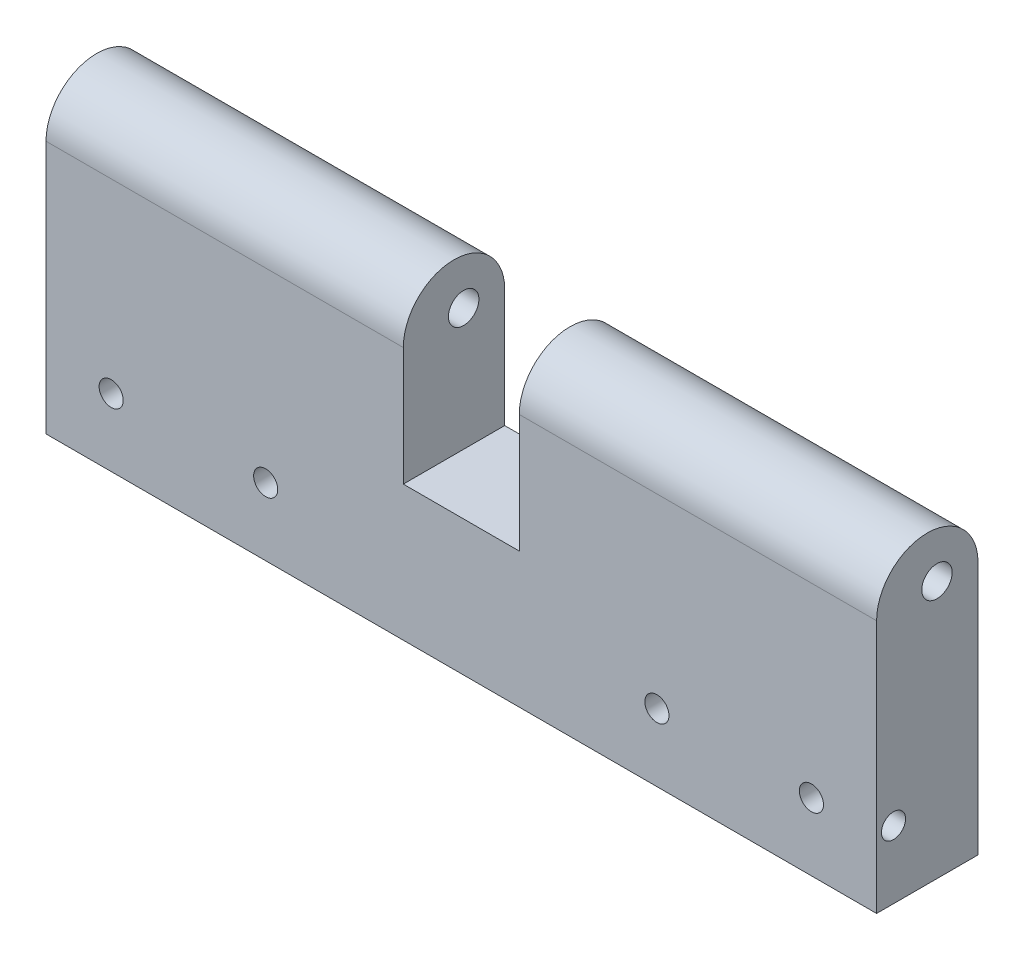
SolidWorks part; units mm, degrees
ref_plane "前视基准面" through (0, 0, 0) normal (0, 0, 1) x (1, 0, 0)
ref_plane "上视基准面" through (0, 0, 0) normal (0, 1, 0) x (1, 0, 0)
ref_plane "右视基准面" through (0, 0, 0) normal (1, 0, 0) x (0, 0, -1)
sketch "草图1" plane through (0, 0, 0) normal (0, 0, 1) x (1, 0, 0)
  line L0 (0, 14) -> (0, -14) construction
  line L1 (86.01, -14) -> (-86.01, -14)
  line L2 (86.01, -14) -> (86.01, 14)
  line L3 (86.01, 14) -> (-86.01, 14)
  line L4 (-86.01, -14) -> (-86.01, 14)
  line L5 (86.01, -14) -> (-86.01, 14) construction
  line L6 (86.01, 14) -> (-86.01, -14) construction
  circle A0 centre (-72.51, 0) radius 2.5
  circle A1 centre (-40.51, 0) radius 2.5
  circle A2 centre (40.51, 0) radius 2.5
  circle A3 centre (72.51, 0) radius 2.5
  point P0 (0, 0)
  dimension "D3" = 13.5
  dimension "D4" = 14
  dimension "D5" = 5
  dimension "D6" = 5
  dimension "D7" = 32
  dimension "D1" = 172.02
  dimension "D2" = 28
extrude "凸台-拉伸1" add sketch "草图1" along normal blind 21
sketch "草图2" plane through (0, 14, 0) normal (0, 1, 0) x (1, 0, 0)
  line L0 (86.01, 0) -> (-86.01, 0) construction
  line L1 (-86.01, 0) -> (-12.01, 0)
  line L2 (-86.01, 0) -> (-86.01, -21)
  line L3 (-86.01, -21) -> (-12.01, -21)
  line L4 (-12.01, 0) -> (-12.01, -21)
  line L5 (86.01, -21) -> (-86.01, -21) construction
  line L6 (86.01, -21) -> (86.01, 0) construction
  line L7 (86.01, 0) -> (12.01, 0)
  line L8 (86.01, 0) -> (86.01, -21)
  line L9 (86.01, -21) -> (12.01, -21)
  line L10 (12.01, 0) -> (12.01, -21)
  dimension "D1" = 74
  dimension "D2" = 74
extrude "凸台-拉伸2" add sketch "草图2" along normal blind 35
sketch "草图3" plane through (86.01, 0, 0) normal (1, 0, 0) x (0, 0, -1)
  line L0 (-21, 49) -> (0, 49) construction
  line L1 (-21, -14) -> (-21, 49) construction
  line L2 (-21, 49) -> (0, 49)
  line L3 (-21, 49) -> (-21, 38.5)
  line L4 (-21, 38.5) -> (0, 38.5)
  line L5 (0, 49) -> (0, 38.5)
  circle A0 centre (-10.5, 38.5) radius 10.5
  line M5 (0, -14) -> (0, 49)
  line M6 (0, 49) -> (-21, 49)
  line M7 (-21, 49) -> (-21, -14)
  dimension "D1" = 10.5
  dimension "D2" = 21
  dimension "D3" = 10.5
extrude "切除-拉伸1" cut sketch "草图3" against normal through all contours A0 M5 M6 | A0 L2 M7 region at (86.01, 46.6546, 18.6546) region at (86.01, 46.6546, 2.3454)
sketch "草图4" plane through (86.01, 0, 0) normal (1, 0, 0) x (0, 0, -1)
  circle A0 centre (-8.5002, 39.35) radius 3.15
  dimension "D1" = 6.3
extrude "切除-拉伸2" cut sketch "草图4" against normal through all
sketch "草图6" plane through (86.01, 0, 0) normal (1, 0, 0) x (0, 0, -1)
  circle A0 centre (-17.5, 0) radius 2.5
extrude "切除-拉伸3" cut sketch "草图6" against normal blind 8
sketch "草图7" plane through (-86.01, 0, 0) normal (-1, 0, 0) x (0, 0, 1)
  circle A0 centre (17.5, 0) radius 2.5
extrude "切除-拉伸4" cut sketch "草图7" against normal blind 8
